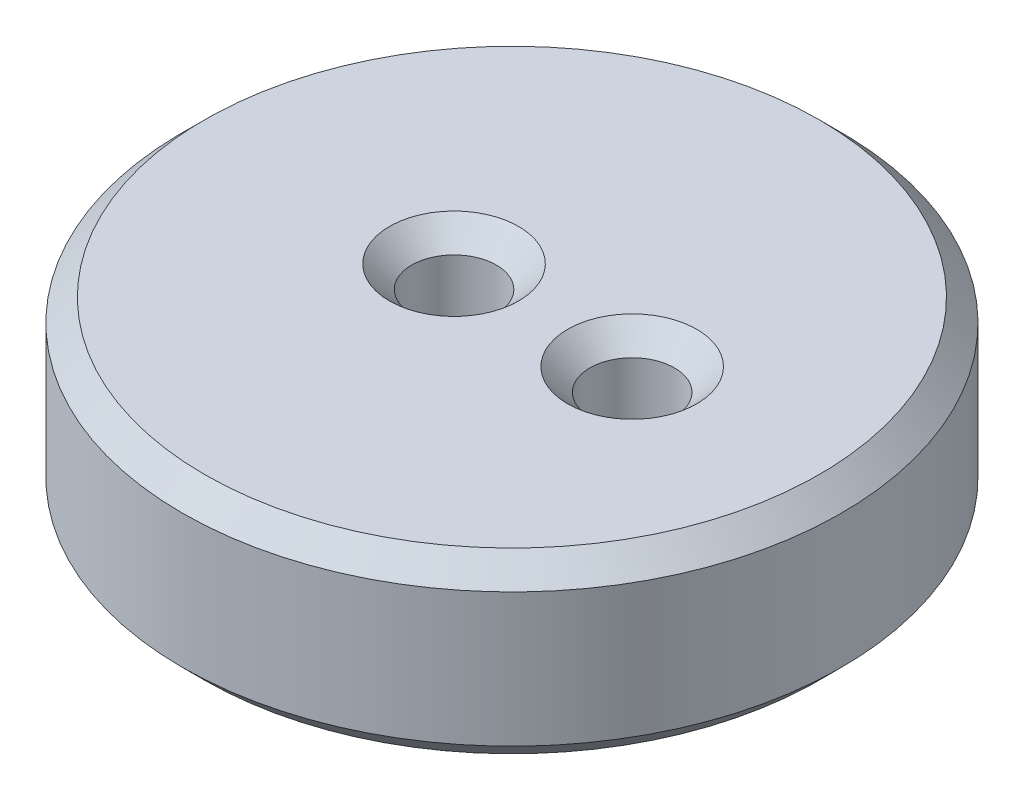
SolidWorks part; units mm, degrees
ref_plane "前视基准面" through (0, 0, 0) normal (0, 0, 1) x (1, 0, 0)
ref_plane "上视基准面" through (0, 0, 0) normal (0, 1, 0) x (1, 0, 0)
ref_plane "右视基准面" through (0, 0, 0) normal (1, 0, 0) x (0, 0, -1)
other "Configuration Table"
sketch "草图1" plane through (0, 0, 0) normal (0, 1, 0) x (1, 0, 0)
  line L0 (0.7, 6.4178) -> (0.7, -6.4114) construction
  line L1 (-5.7349, 0) -> (5.8104, 0) construction
  circle A0 centre (0, 0) radius 7.4
  circle A1 centre (2.7, 0) radius 0.95
  circle A2 centre (-1.3, 0) radius 0.95
  dimension "D1" = 14.8
  dimension "D3" = 4
  dimension "D4" = 1.9
  dimension "D2" = 0.7
extrude "凸台-拉伸1" add sketch "草图1" along normal blind 4
chamfer "倒角1" distance 0.5 angle 45 6 edges at (0, 0, 7.4) (0, 4, 7.4) (-1.3, 0, -0.95) (2.7, 0, 0.95) (-1.3, 4, -0.95) (2.7, 4, 0.95)
ref_axis "基准轴1" through (0, 3.5, 0) along (0, -1, 0)
sketch "草图2" plane through (0, 0, 0) normal (0, 1, 0) x (1, 0, 0)
  line L0 (-5.9042, 0) -> (6.2358, 0) construction
